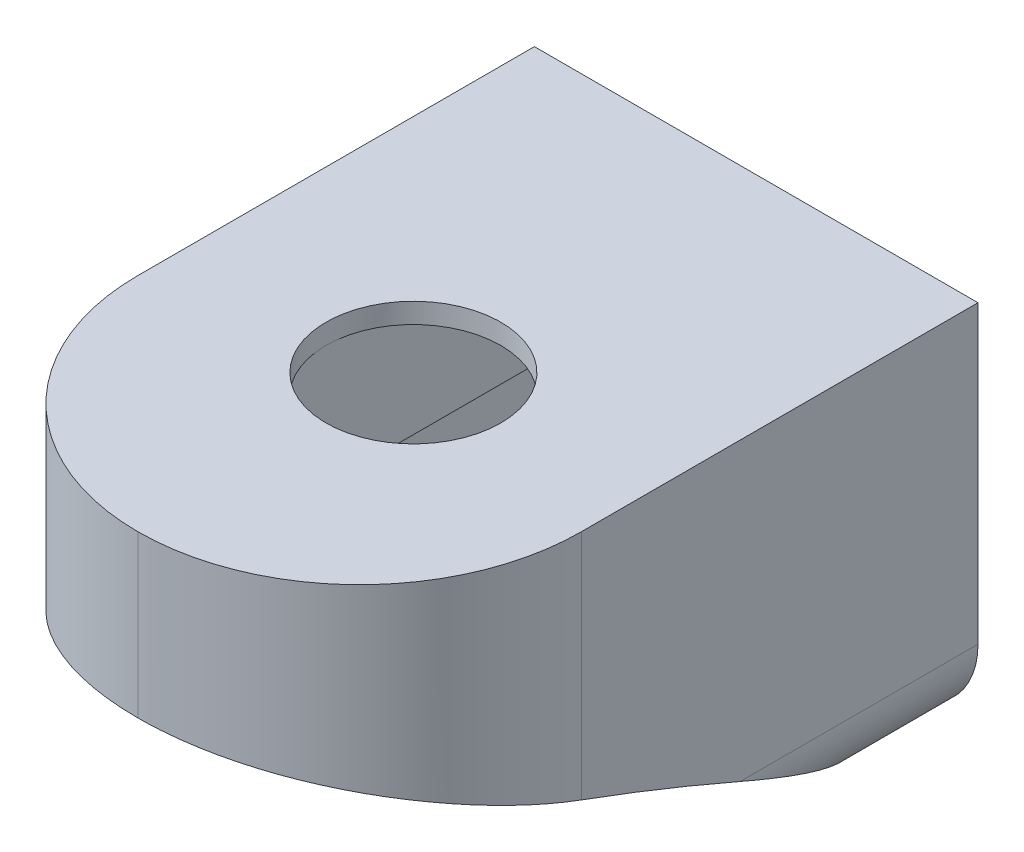
SolidWorks part; units mm, degrees
ref_plane "Front Plane" through (0, 0, 0) normal (0, 0, 1) x (1, 0, 0)
ref_plane "Top Plane" through (0, 0, 0) normal (0, 1, 0) x (1, 0, 0)
ref_plane "Right Plane" through (0, 0, 0) normal (1, 0, 0) x (0, 0, -1)
sketch "Sketch1" plane through (0, 0, 0) normal (0, 0, 1) x (1, 0, 0)
  line L1 (-16.5, 14) -> (16.5, 14)
  line L2 (-16.5, 14) -> (-16.5, -14)
  line L3 (-16.5, -14) -> (16.5, -14)
  line L4 (16.5, 14) -> (16.5, -14)
  line L5 (-16.5, 14) -> (16.5, -14) construction
  line L6 (-16.5, -14) -> (16.5, 14) construction
  point P0 (0, 0)
  dimension "D1" = 33
  dimension "D2" = 28
extrude "Boss-Extrude1" add sketch "Sketch1" along normal blind 46
sketch "Sketch2" plane through (16.5, 0, 0) normal (1, 0, 0) x (0, 0, -1)
  line L0 (-46, -14) -> (0, -14) construction
  line L1 (-46, -14) -> (-46, 14) construction
  line L2 (-46, 2) -> (-46, -14)
  line L3 (-46, -14) -> (-5, -14)
  spline S0 degree 2 poles (-5, -14) (-24.7874, -3.8546) (-46, 2) knots 0 0 0 1 1 1
  dimension "D3" = 44.0114
  dimension "D1" = 5
  dimension "D2" = 12
extrude "Cut-Extrude2" cut sketch "Sketch2" against normal through all
sketch "Sketch3" plane through (16.5, 0, 0) normal (1, 0, 0) x (0, 0, -1)
  line L0 (-5, -14) -> (-2.5, -14)
  line L1 (-5, -14) -> (0, -14) construction
  line L2 (-2.5, -14) -> (-2.5, 3.5)
  line L3 (-2.5, 3.5) -> (-40.5, 3.5)
  line L4 (-40.5, 3.5) -> (-40.5, 0.4026)
  parabola Q0 (-5, -14) -> (-46, 2) focus (-69.1548, -102.5729) apex (-35.4828, -1.1955) construction
  parabola Q1 (-5, -14) -> (-46, 2) focus (-69.1548, -102.5729) apex (-35.4828, -1.1955) construction
  parabola Q2 (-5, -14) -> (-40.5, 0.4026) focus (-69.1548, -102.5729) apex (-35.4828, -1.1955)
  dimension "D1" = 17.5
  dimension "D2" = 38
extrude "Cut-Extrude3" cut sketch "Sketch3" against normal blind 27 from offset 3 offset against normal yes
fillet "Fillet1" radius 12.5 2 edges at (13.5, 1.9513, 40.5) (-13.5, 1.9513, 40.5)
fillet "Fillet2" radius 16.5 2 edges at (16.5, 8, 46) (-16.5, 8, 46)
fillet "Fillet3" radius 6 2 edges at (16.5, -14, 2.5) (-16.5, -14, 2.5)
sketch "Sketch4" plane through (0, 3.5, 0) normal (0, -1, 0) x (1, 0, 0)
  line L0 (0, 2.5) -> (0, 40.5) construction
  line L1 (-13.5, 2.5) -> (13.5, 2.5) construction
  line L2 (-1, 40.5) -> (1, 40.5) construction
  line L3 (-10.5, 2.5) -> (10.5, 2.5) construction
  line L4 (-6.5, 32) -> (6.5, 32)
  line L5 (-6.5, 32) -> (-6.5, 9)
  line L6 (-6.5, 9) -> (6.5, 9)
  line L7 (6.5, 32) -> (6.5, 9)
  line L8 (-6.5, 32) -> (6.5, 9) construction
  line L9 (-6.5, 9) -> (6.5, 32) construction
  point P6 (0, 20.5)
  dimension "D1" = 6.5
  dimension "D2" = 23
  dimension "D3" = 13
extrude "Cut-Extrude4" cut sketch "Sketch4" against normal blind 9
sketch "Sketch5" plane through (0, 12.5, 0) normal (0, -1, 0) x (1, 0, 0)
  line L0 (0, 32) -> (0, 9) construction
  line L1 (6.5, 32) -> (-6.5, 32) construction
  line L2 (-6.5, 9) -> (6.5, 9) construction
  circle A0 centre (0, 25.5) radius 6.5
  dimension "D1" = 13
extrude "Cut-Extrude5" cut sketch "Sketch5" against normal through all
sketch "Sketch6" plane through (0, 3.5, 0) normal (0, -1, 0) x (1, 0, 0)
  line L0 (-6.5, 20.5) -> (6.5, 20.5) construction
  line L1 (-6.5, 32) -> (-6.5, 9) construction
  line L2 (6.5, 9) -> (6.5, 32) construction
  line L3 (0, 6.7) -> (0, 34.3) construction
  circle A0 centre (0, 34.3) radius 1
  circle A1 centre (0, 6.7) radius 1
  point P10 (0, 20.5)
  dimension "D2" = 2
  dimension "D1" = 27.6
extrude "Cut-Extrude6" cut sketch "Sketch6" against normal blind 8
sketch "Sketch7" plane through (0, 0, 0) normal (0, 0, -1) x (-1, 0, 0)
  line L0 (0, 0) -> (-24.291, 0) construction
  line L1 (-16.5, -8) -> (-16.5, 14) construction
  circle A0 centre (-9.5, 0) radius 1
  circle A1 centre (-5, 0) radius 2.5
  circle A2 centre (-0.5, 0) radius 1
  dimension "D1" = 2
  dimension "D2" = 5
  dimension "D3" = 2
  dimension "D4" = 11.5
  dimension "D5" = 9
  dimension "D6" = 4.5
extrude "Cut-Extrude7" cut sketch "Sketch7" against normal up to surface (2.5 mm away) up to face at (0, -7.9645, 2.5)
